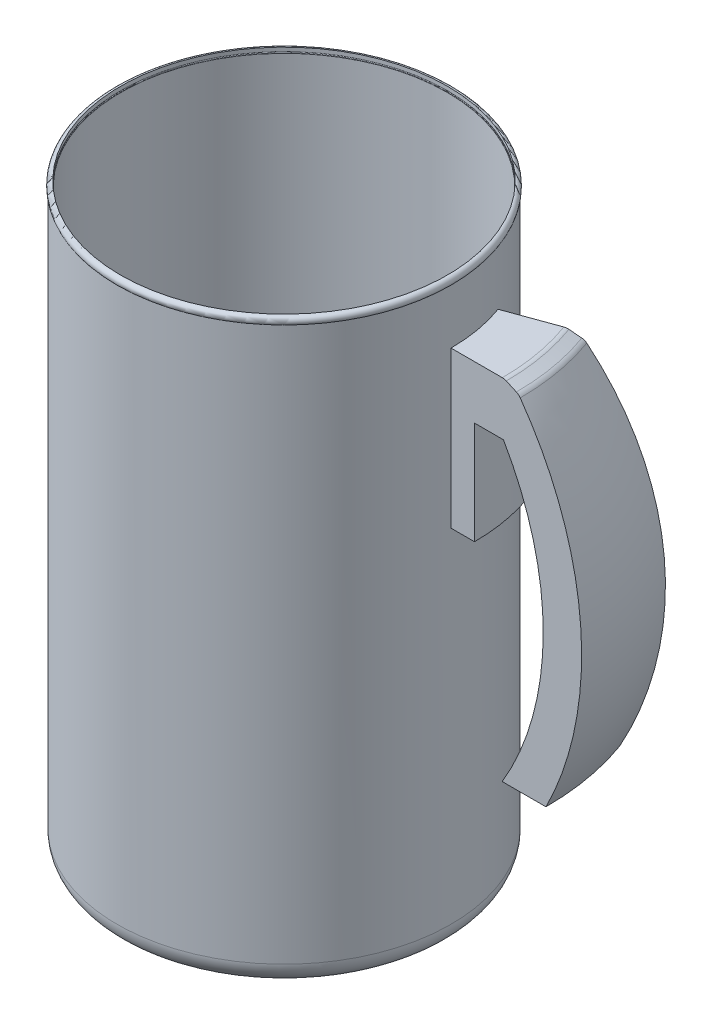
SolidWorks part; units mm, degrees
ref_plane "Front Plane" through (0, 0, 0) normal (0, 0, 1) x (1, 0, 0)
ref_plane "Top Plane" through (0, 0, 0) normal (0, 1, 0) x (1, 0, 0)
ref_plane "Right Plane" through (0, 0, 0) normal (1, 0, 0) x (0, 0, -1)
sketch "Sketch1" plane through (0, 0, 0) normal (0, 0, 1) x (1, 0, 0)
  line L0 (0, 0) -> (0, 316.8923) construction
  line L1 (0, 15.1909) -> (-75, 15.1909)
  line L2 (-85, 25.1909) -> (-85, 314.4808)
  line L3 (-85.1655, 314.6463) -> (-85.1844, 314.6463)
  line L4 (0, 15.1909) -> (0, 315.1909)
  line L5 (-85.1844, 315.1909) -> (0, 315.1909)
  arc A0 (-85.1844, 315.1909) -> (-85.1844, 314.6463) centre (-85.1844, 314.9186) ccw
  arc A1 (-85.1655, 314.6463) -> (-85, 314.4808) centre (-85.1655, 314.4808) cw
  arc A2 (-75, 15.1909) -> (-85, 25.1909) centre (-75, 25.1909) cw
  dimension "D3" = 10
  dimension "D1" = 170
  dimension "D4" = 300
revolve "Revolve1" add sketch "Sketch1" angle 360 about L4
shell "Shell7" thickness 2 removed face at (0, 315.1909, -85.1844) outward yes
sketch "Sketch4" plane through (0, 0, 0) normal (0, 0, 1) x (1, 0, 0)
  line L0 (87, 285.1658) -> (113.7412, 285.1658)
  line L1 (87, 25.1909) -> (87, 313.5522) construction
  line L2 (115.793, 284.7255) -> (121.0361, 282.3661)
  line L3 (87, 203.914) -> (99.2279, 203.914)
  line L4 (99.2279, 203.914) -> (99.2279, 257.4468)
  line L5 (99.2279, 257.4468) -> (114.2959, 257.4468)
  line L6 (113.6555, 102.9267) -> (136.4617, 102.9267)
  line L7 (87, 285.1658) -> (87, 203.914)
  line L8 (0, 0) -> (0, 519.2789) construction
  arc A0 (123.0565, 280.7077) -> (136.4617, 102.9267) centre (-17.2717, 180.7307) cw
  arc A1 (114.2959, 257.4468) -> (113.6555, 102.9267) centre (-17.2717, 180.7307) cw
  arc A2 (123.0565, 280.7077) -> (121.0361, 282.3661) centre (118.9843, 277.8064) ccw
  arc A3 (115.793, 284.7255) -> (113.7412, 285.1658) centre (113.7412, 280.1658) ccw
  dimension "D1" = 20
  dimension "D2" = 5
  dimension "D3" = 5
revolve "Revolve2" add sketch "Sketch4" angle 20 about L8
